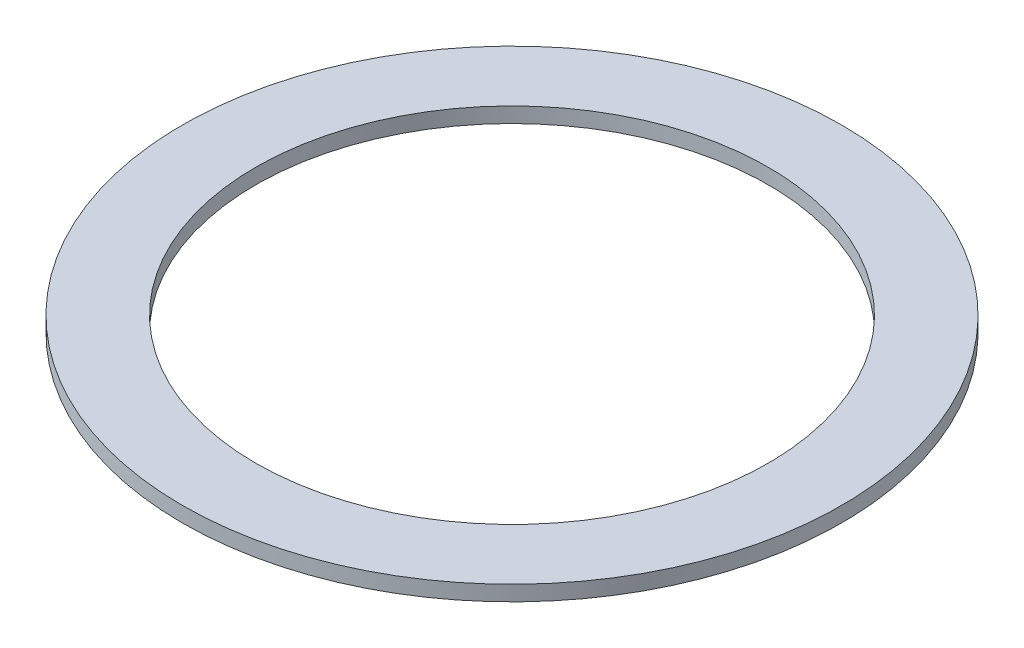
SolidWorks part; units mm, degrees
ref_plane "Front Plane" through (0, 0, 0) normal (0, 0, 1) x (1, 0, 0)
ref_plane "Top Plane" through (0, 0, 0) normal (0, 1, 0) x (1, 0, 0)
ref_plane "Right Plane" through (0, 0, 0) normal (1, 0, 0) x (0, 0, -1)
sketch "Sketch1" plane through (0, 0, 0) normal (0, 1, 0) x (1, 0, 0)
  circle A0 centre (0, 0) radius 26.67
  circle A1 centre (0, 0) radius 34.29
  dimension "D1" = 53.34
  dimension "D2" = 68.58
extrude "Boss-Extrude1" add sketch "Sketch1" along normal blind 1.5875
equation "\"D1@Sketch1\"=2.1in"
equation "\"D2@Sketch1\"=2.7in"
